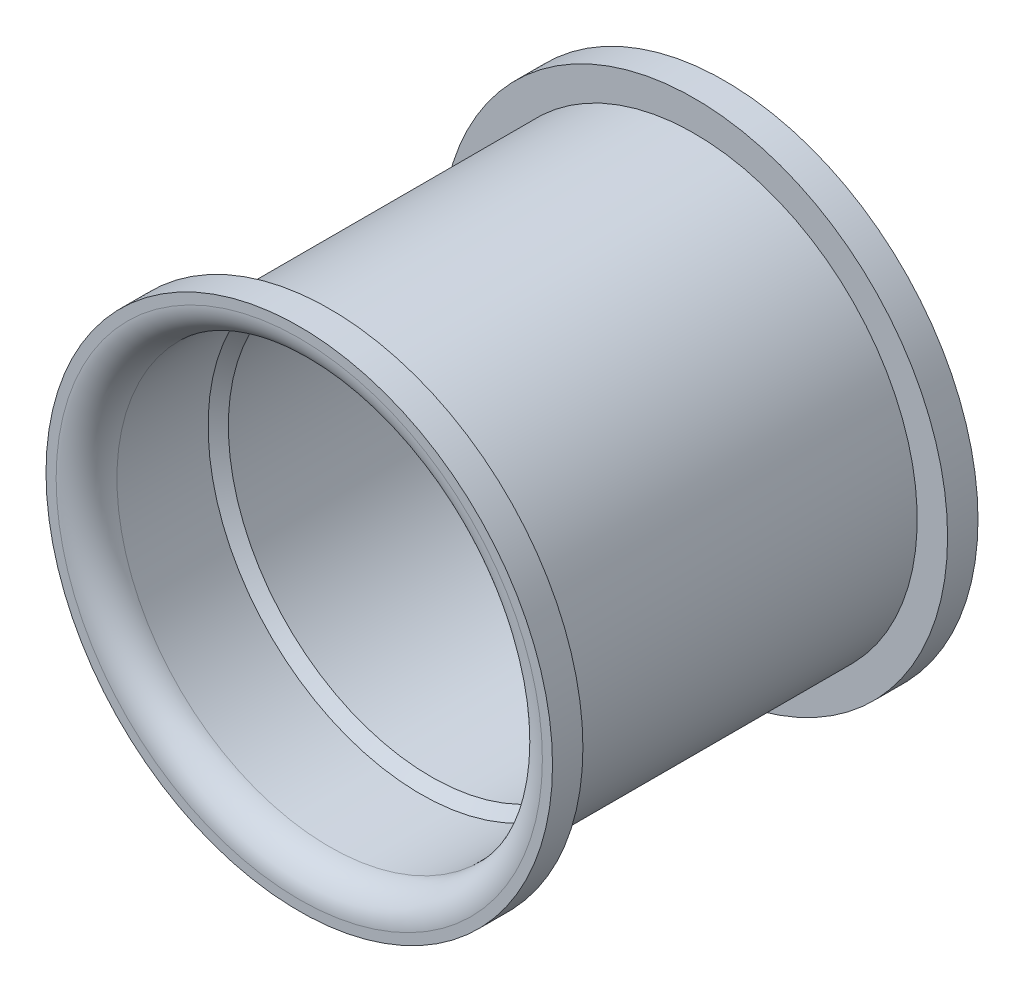
SolidWorks part; units mm, degrees
material "PET"
ref_plane "Plano frontal" through (0, 0, 0) normal (0, 0, 1) x (1, 0, 0)
ref_plane "Plano superior" through (0, 0, 0) normal (0, 1, 0) x (1, 0, 0)
ref_plane "Plano direito" through (0, 0, 0) normal (1, 0, 0) x (0, 0, -1)
sketch "Esboço1" plane through (0, 0, 0) normal (0, 0, 1) x (1, 0, 0)
  circle A0 centre (0, 0) radius 12.5
extrude "Ressalto-extrusão1" add sketch "Esboço1" along normal blind 21
sketch "Esboço4" plane through (0, 0, 0) normal (1, 0, 0) x (0, 0, -1)
  line L0 (-19.5, -12.5) -> (-19.5, -11)
  line L1 (-21, -12.5) -> (0, -12.5) construction
  line L2 (-19.5, -11) -> (-1.5, -11)
  line L3 (-1.5, -11) -> (-1.5, -12.5)
  line L4 (-1.5, -12.5) -> (-19.5, -12.5)
  line L5 (-21, 12.5) -> (-21, -12.5) construction
  line L6 (0, -12.5) -> (0, 12.5) construction
  line L7 (2.777, 0) -> (-25.9349, 0) construction
  dimension "D1" = 1.5
  dimension "D2" = 1.5
  dimension "D3" = 1.5
revolve "Corte-Revolução1" cut sketch "Esboço4" angle 360 about L7
sketch "Esboço5" plane through (0, 0, 21) normal (0, 0, 1) x (1, 0, 0)
  circle A0 centre (0, 0) radius 9.25
extrude "Corte-extrusão1" cut sketch "Esboço5" against normal blind 14
sketch "Esboço6" plane through (0, 0, 7) normal (0, 0, 1) x (1, 0, 0)
  line L0 (-1.6493, 0.0483) -> (-0.196, 1.6383)
  arc A0 (-1.6493, 0.0483) -> (-0.196, 1.6383) centre (0, 0) ccw
  dimension "D1" = 3.3
  dimension "D2" = 1.25
extrude "Corte-extrusão2" cut sketch "Esboço6" against normal blind 17
sketch "Esboço7" plane through (0, 0, 7) normal (0, 0, 1) x (1, 0, 0)
  circle A0 centre (6.2, 0) radius 2.5
  circle A1 centre (1.9159, -5.8966) radius 2.5
  circle A2 centre (-5.0159, -3.6443) radius 2.5
  circle A3 centre (-5.0159, 3.6443) radius 2.5
  circle A4 centre (1.9159, 5.8966) radius 2.5
  point P13 (0, 0)
  dimension "D1" = 5
  dimension "D3" = 6.2
  dimension "D2" = 0
  dimension "D4" = 5
extrude "Corte-extrusão3" cut sketch "Esboço7" against normal blind 17
sketch "Esboço10" plane through (0, 0, 0) normal (0, 0, -1) x (-1, 0, 0)
  circle A0 centre (0, 0) radius 12
  dimension "D1" = 24
sketch "Esboço11" plane through (0, 0, 7) normal (0, 0, 1) x (1, 0, 0)
  circle A0 centre (0, 0) radius 10
  dimension "D1" = 20
extrude "Corte-extrusão4" cut sketch "Esboço11" along normal through all
chamfer "Chanfro3" distance 0.5 angle 45 2 edges at (-0.9227, 0.8433, 0) (1.2179, -1.1132, 0)
fillet "Filete2" radius 1 1 edges at (-11, 0, 19.5)
sketch "Esboço12" plane through (0, 0, 7) normal (0, 0, 1) x (1, 0, 0)
  circle A0 centre (0, 0) radius 4.25
  dimension "D1" = 8.5
extrude "Corte-extrusão5" cut sketch "Esboço12" against normal blind 4.5
sketch "Esboço13" plane through (0, 0, 7) normal (0, 0, 1) x (1, 0, 0)
  circle A0 centre (0, 0) radius 10
extrude "Corte-extrusão6" cut sketch "Esboço13" against normal blind 2
sketch "Esboço14" plane through (0, 0, 21) normal (0, 0, 1) x (1, 0, 0)
  circle A0 centre (0, 0) radius 10.5
  dimension "D1" = 21
extrude "Corte-extrusão7" cut sketch "Esboço14" against normal blind 6
chamfer "Chanfro5" distance 0.5 angle 45 1 edges at (10, 0, 15)
fillet "Filete3" radius 1.5 1 edges at (10.5, 0, 21)
fillet "Filete4" radius 0.5 10 edges at (-2.5262, 3.4177, 3.75) (0.0348, 4.2499, 3.75) (2.4698, 3.4587, 3.75) (4.0526, 1.2801, 3.75) (4.0526, -1.2801, 3.75) (2.4698, -3.4587, 3.75) (0.0348, -4.2499, 3.75) (-2.5262, -3.4177, 3.75) (-4.0311, -1.3464, 3.75) (-4.0311, 1.3464, 3.75)
